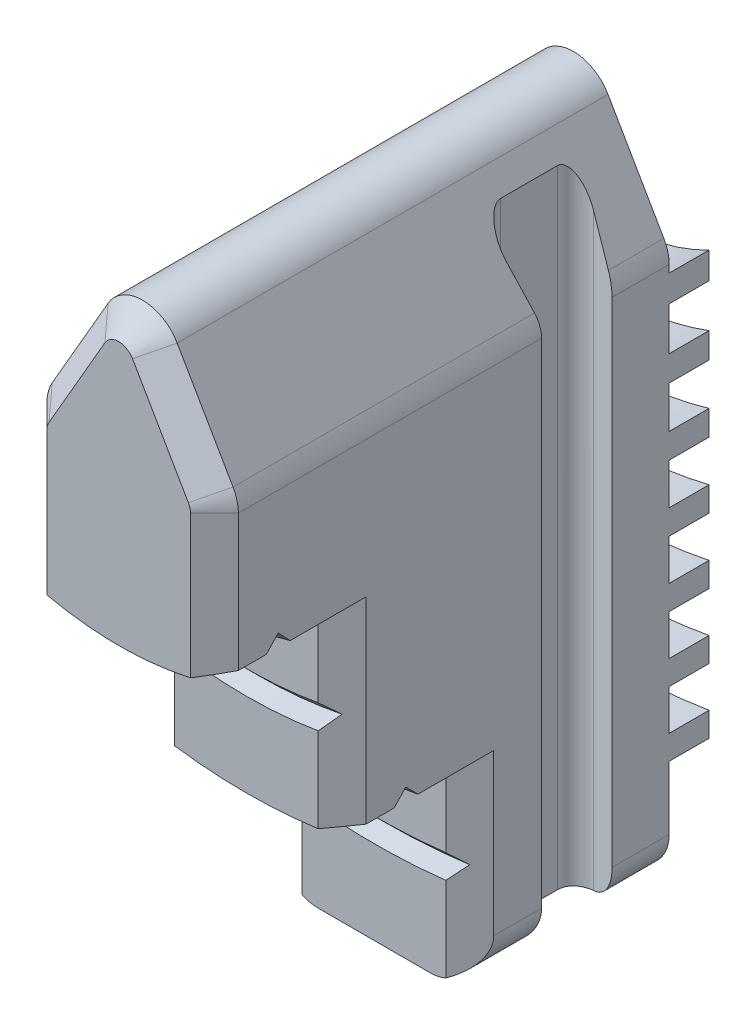
SolidWorks part; units mm, degrees
material "Alloy Steel"
ref_plane "Front Plane" through (0, 0, 0) normal (0, 0, 1) x (1, 0, 0)
ref_plane "Top Plane" through (0, 0, 0) normal (0, 1, 0) x (1, 0, 0)
ref_plane "Right Plane" through (0, 0, 0) normal (1, 0, 0) x (0, 0, -1)
sketch "Sketch1" plane through (0, 0, 0) normal (0, 0, 1) x (1, 0, 0)
  line L0 (-4.3301, -7.5) -> (-11.3301, -19.6244)
  line L1 (-12, -22.1244) -> (-12, -84)
  line L2 (-7, -89) -> (7, -89)
  line L3 (12, -84) -> (12, -22.1244)
  line L4 (11.3301, -19.6244) -> (4.3301, -7.5)
  arc A0 (-12, -84) -> (-7, -89) centre (-7, -84) ccw
  arc A1 (7, -89) -> (12, -84) centre (7, -84) ccw
  arc A2 (12, -22.1244) -> (11.3301, -19.6244) centre (7, -22.1244) ccw
  arc A3 (-11.3301, -19.6244) -> (-12, -22.1244) centre (-7, -22.1244) ccw
  arc A4 (-4.3301, -7.5) -> (4.3301, -7.5) centre (0, -10) cw
  arc A5 (22.598, -34.2101) -> (-22.598, -34.2101) centre (0, 0) cw construction
  arc A6 (-32.5, -56.2917) -> (33.4047, -55.7595) centre (0, 0) ccw construction
  point P9 (-12, -89)
  point P12 (12, -89)
  point P15 (12, -20.7846)
  point P18 (-12, -20.7846)
  point P21 (0, 0)
  dimension "D4" = 5
  dimension "D5" = 41
  dimension "D6" = 24
  dimension "D1" = 60
  dimension "D2" = 24
  dimension "D3" = 89
extrude "Boss-Extrude1" add sketch "Sketch1" along normal blind 57 from offset 5
sketch "Sketch7" plane through (0, 0, 0) normal (1, 0, 0) x (0, 0, -1)
  line L0 (0, 0) -> (-103.2261, 0) construction
  line L1 (-62, 0) -> (-62, -99.6002) construction
  line L2 (-62, -89) -> (-1.8317, -89) construction
  line L3 (-62, -89) -> (-5, -89) construction
  line L4 (-62, -84) -> (-62, -89) construction
  line L5 (-62, -41) -> (-46, -41)
  line L6 (-46, -41) -> (-46, -65)
  line L7 (-46, -65) -> (-30, -65)
  line L8 (-30, -65) -> (-30, -89)
  line L9 (-30, -89) -> (-30, -99.2003)
  line L10 (-30, -99.2003) -> (-73.3918, -99.2003)
  line L11 (-73.3918, -99.2003) -> (-73.3918, -41)
  line L12 (-73.3918, -41) -> (-62, -41)
  line L13 (-5, -5) -> (-62, -5) construction
  line L14 (-62, -41) -> (-46, -41) construction
  line L15 (-54, -41) -> (-54, -30.0717) construction
  line L16 (-38, -65) -> (-38, -56.2829) construction
  line L17 (-55.5, -41) -> (-54, -39.5)
  line L18 (-54, -39.5) -> (-52.5, -41)
  line L19 (-46, -53) -> (-38, -53) construction
  line L20 (-30, -77) -> (-22.891, -77) construction
  line L21 (-44.5, -53) -> (-46, -51.5)
  line L22 (-44.5, -53) -> (-46, -54.5)
  line L23 (-46, -54.5) -> (-46, -51.5)
  line L24 (-55.5, -41) -> (-52.5, -41)
  line L25 (-38, -63.5) -> (-39.5, -65)
  line L26 (-38, -63.5) -> (-36.5, -65)
  line L27 (-36.5, -65) -> (-39.5, -65)
  line L28 (-28.5, -77) -> (-30, -75.5)
  line L29 (-30, -75.5) -> (-30, -78.5)
  line L30 (-30, -78.5) -> (-28.5, -77)
  dimension "D1" = 36
  dimension "D2" = 24
  dimension "D3" = 24
  dimension "D4" = 16
  dimension "D5" = 16
  dimension "D6" = 90
  dimension "D7" = 1.5
  dimension "D8" = 90
  dimension "D9" = 1.5
  dimension "D10" = 90
  dimension "D11" = 1.5
  dimension "D12" = 90
  dimension "D13" = 1.5
revolve "Cut-Revolve2" cut sketch "Sketch7" angle 360 about L0 region at (0, -73.1665, 54.1518)
sketch "Sketch8" plane through (0, 0, 0) normal (1, 0, 0) x (0, 0, -1)
  line L0 (-22.8698, 0) -> (35.2204, 0) construction
  line L1 (-5, 0) -> (-5, -115.7433) construction
  line L2 (0, 36.2476) -> (0, -36.2476) construction
  line L3 (-5, -34) -> (-5, -37)
  line L4 (-5, -26) -> (0, -26)
  line L5 (-5, -26) -> (-5, -29)
  line L6 (-5, -29) -> (0, -29)
  line L7 (0, -26) -> (0, -29)
  line L8 (-5, -34) -> (0, -34)
  line L9 (0, -34) -> (0, -37)
  line L10 (-5, -37) -> (0, -37)
  line L11 (-5, -42) -> (-5, -45)
  line L12 (-5, -42) -> (0, -42)
  line L13 (0, -42) -> (0, -45)
  line L14 (-5, -45) -> (0, -45)
  line L15 (-5, -50) -> (-5, -53)
  line L16 (-5, -50) -> (0, -50)
  line L17 (0, -50) -> (0, -53)
  line L18 (-5, -53) -> (0, -53)
  line L19 (-5, -58) -> (-5, -61)
  line L20 (-5, -58) -> (0, -58)
  line L21 (0, -58) -> (0, -61)
  line L22 (-5, -61) -> (0, -61)
  line L23 (-5, -66) -> (-5, -69)
  line L24 (-5, -66) -> (0, -66)
  line L25 (0, -66) -> (0, -69)
  line L26 (-5, -69) -> (0, -69)
  line L27 (-5, -74) -> (-5, -77)
  line L28 (-5, -74) -> (0, -74)
  line L29 (0, -74) -> (0, -77)
  line L30 (-5, -77) -> (0, -77)
  dimension "D1" = 5
  dimension "D2" = 26
  dimension "D3" = 3
  dimension "D4" = 7
revolve "Revolve1" add sketch "Sketch8" angle 90 mid plane about L0
sketch "Sketch9" plane through (0, 0, 0) normal (0, 1, 0) x (1, 0, 0)
  line L0 (0, 17.4038) -> (-12, 17.4038) construction
  line L1 (0, 25.0392) -> (12, 25.0392) construction
  line L2 (0, -48.95) -> (0, 48.95) construction
  line L3 (-12, 17.4038) -> (-75.5638, 17.4038)
  line L4 (-12, 17.4038) -> (-12, -74.9712)
  line L5 (-12, -74.9712) -> (-75.5638, -74.9712)
  line L6 (-75.5638, 17.4038) -> (-75.5638, -74.9712)
  line L7 (12, 25.0392) -> (78.2798, 25.0392)
  line L8 (12, 25.0392) -> (12, -78.7766)
  line L9 (12, -78.7766) -> (78.2798, -78.7766)
  line L10 (78.2798, 25.0392) -> (78.2798, -78.7766)
  dimension "D1" = 12
  dimension "D2" = 12
extrude "Cut-Extrude2" cut sketch "Sketch9" against normal blind 100
sketch "Sketch10" plane through (0, 0, 0) normal (0, 1, 0) x (1, 0, 0)
  line L0 (-20.4861, -13) -> (24.7961, -13) construction
  line L1 (-36.2476, 0) -> (36.2476, 0) construction
  line L2 (-12, 52.3359) -> (-12, 20.9094) construction
  line L3 (0, -48.95) -> (0, 48.95) construction
  line L5 (-12, -13) -> (-12, -21)
  line L6 (-12, -21) -> (-8.6014, -22.0716)
  line L7 (-6, -13) -> (-6, -20.1641)
  line L9 (-6, -16.5821) -> (-16.3664, -16.5821) construction
  line L10 (-12, -12.1641) -> (-8.6014, -11.0926)
  line L11 (-12, -20.1641) -> (-12, -12.1641)
  line L12 (12, -20.1641) -> (12, -12.1641)
  line L13 (12, -12.1641) -> (8.6014, -11.0926)
  line L14 (6, -13) -> (6, -20.1641)
  line L15 (12, -21) -> (8.6014, -22.0716)
  line L16 (12, -13) -> (12, -21)
  arc A3 (-8.6014, -22.0716) -> (-6, -20.1641) centre (-8, -20.1641) ccw
  arc A4 (-8.6014, -11.0926) -> (-6, -13) centre (-8, -13) cw
  arc A5 (8.6014, -11.0926) -> (6, -13) centre (8, -13) ccw
  arc A6 (8.6014, -22.0716) -> (6, -20.1641) centre (8, -20.1641) cw
  dimension "D5" = 6
  dimension "D7" = 2
  dimension "D1" = 13
  dimension "D2" = 12
  dimension "D3" = 8
  dimension "D6" = 6
extrude "Cut-Extrude3" cut sketch "Sketch10" against normal blind 100 contours A6 L15 L16 L12 L13 A5 L14 | A4 L10 L11 L5 L6 A3 L7 region at (-8.9473, 0, 16.5821) region at (8.9473, 0, 16.5821)
chamfer "Chamfer4" distance 3 angle 45 1 edges at (12, -44.6435, 46)
chamfer "Chamfer5" distance 3 angle 45 7 edges at (-12, -30.6645, 62) (12, -30.6645, 62) (11.8296, -20.8303, 62) (7.8301, -13.5622, 62) (0, -5, 62) (-11.8296, -20.8303, 62) (-7.8301, -13.5622, 62)
chamfer "Chamfer7" distance 3 angle 45 1 edges at (-12, -58.5226, 46)
chamfer "Chamfer10" distance 3 angle 45 2 edges at (12, -69.2115, 30) (-12, -69.2115, 30)
